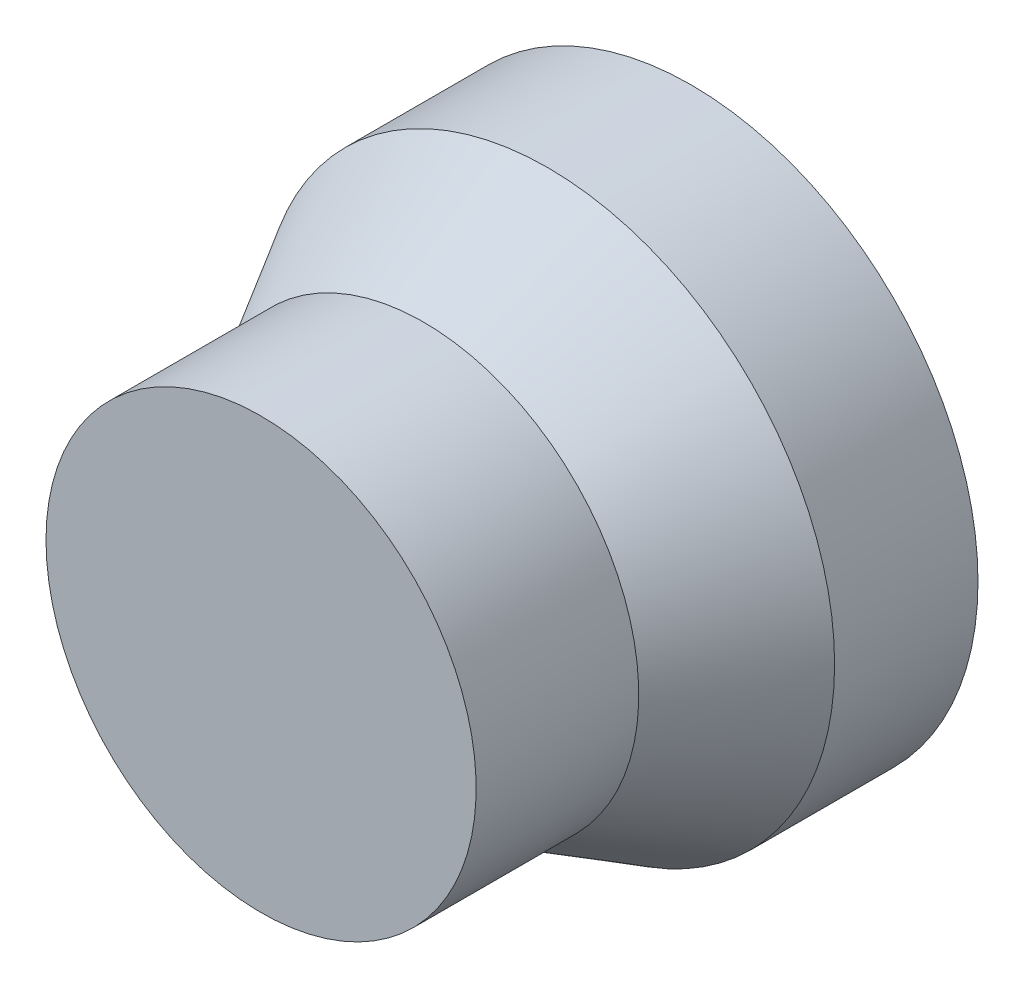
SolidWorks part; units mm, degrees
ref_plane "Front Plane" through (0, 0, 0) normal (0, 0, 1) x (1, 0, 0)
ref_plane "Top Plane" through (0, 0, 0) normal (0, 1, 0) x (1, 0, 0)
ref_plane "Right Plane" through (0, 0, 0) normal (1, 0, 0) x (0, 0, -1)
sketch "Sketch1" plane through (0, 0, 0) normal (0, 1, 0) x (1, 0, 0)
  line L0 (0, 165.5738) -> (0, -211.4754) construction
  line L1 (0, -150) -> (75, -150)
  line L2 (75, -150) -> (75, -93.3013)
  line L3 (75, -93.3013) -> (100, -50)
  line L4 (100, -50) -> (100, 0)
  line L5 (100, 0) -> (0, 0)
  line L6 (0, 0) -> (0, -150)
  point P5 (75, -82.2837)
  dimension "D1" = 75
  dimension "D2" = 100
  dimension "D3" = 150
  dimension "D4" = 50
  dimension "D5" = 30
revolve "Revolve1" add sketch "Sketch1" angle 360 about L0
equation "\"base_link_diameter\"=75"
equation "\"base_link_length\"=150"
equation "\"D1\"= \"base_link_length\""
equation "\"link2_diameter\"=150"
equation "\"link2_length\"=300"
equation "\"link3_diameter\"=150"
equation "\"link3_length\"=150"
equation "\"link4_diameter\"=150"
equation "\"link4_length\"=150"
equation "\"link5_diameter\"=150"
equation "\"link5_length\"=200"
equation "\"end_effector_diameter\"=150"
equation "\"end_effector_length\"=150"
equation "\"base_link_diameterA\"=200"
equation "\"base_link_diameterB\"=150"
equation "\"D1@Sketch1\"=\"base_link_diameterB\"/2"
equation "\"D2@Sketch1\"=\"base_link_diameterA\"/2"
equation "\"D3@Sketch1\"=\"base_link_length\""
equation "\"base_link_lengthA\"=50"
equation "\"D4@Sketch1\"=\"base_link_lengthA\""
equation "\"link1_diameter\"=150"
equation "\"link1_length\"=150"
